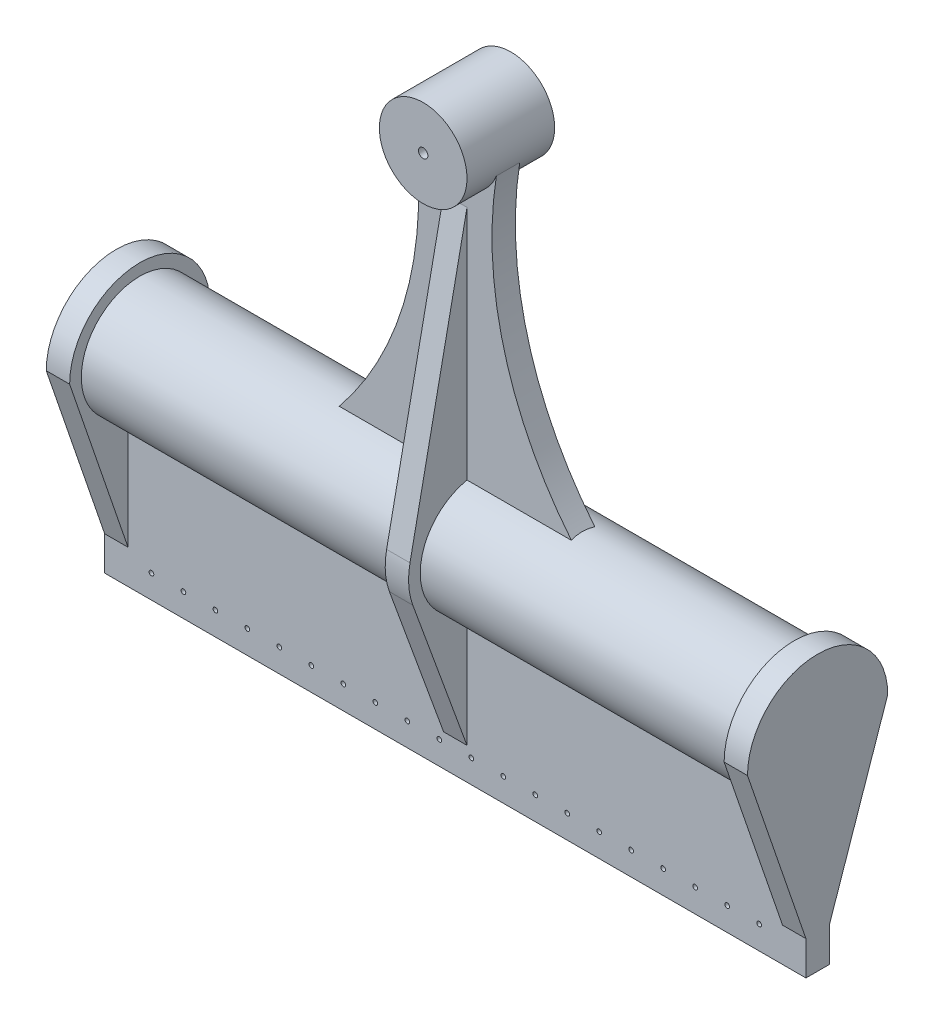
SolidWorks part; units mm, degrees
ref_plane "Front Plane" through (0, 0, 0) normal (1, 0, 0) x (0, 1, 0)
ref_plane "Top Plane" through (0, 0, 0) normal (0, 0, 1) x (0, 1, 0)
ref_plane "Right Plane" through (0, 0, 0) normal (0, 1, 0) x (-1, 0, 0)
sketch "Coefficients Plate Sketch" plane through (0, 0, 0) normal (0, 0, 1) x (0, 1, 0)
  line L1 (-44.45, -76.2) -> (0, -76.2)
  line L2 (-44.45, -76.2) -> (-44.45, 76.2)
  line L3 (-44.45, 76.2) -> (0, 76.2)
  line L4 (0, -76.2) -> (0, 76.2)
  line L5 (-44.45, -76.2) -> (0, 76.2) construction
  line L6 (-44.45, 76.2) -> (0, -76.2) construction
  circle A0 centre (-39.37, -66.04) radius 0.508
  circle A1 centre (-39.37, -59.0884) radius 0.508
  circle A2 centre (-39.37, -52.1368) radius 0.508
  circle A3 centre (-39.37, -45.1853) radius 0.508
  circle A4 centre (-39.37, -38.2337) radius 0.508
  circle A5 centre (-39.37, -31.2821) radius 0.508
  circle A6 centre (-39.37, -24.3305) radius 0.508
  circle A7 centre (-39.37, -17.3789) radius 0.508
  circle A8 centre (-39.37, -10.4274) radius 0.508
  circle A9 centre (-39.37, -3.4758) radius 0.508
  circle A10 centre (-39.37, 3.4758) radius 0.508
  circle A11 centre (-39.37, 10.4274) radius 0.508
  circle A12 centre (-39.37, 17.3789) radius 0.508
  circle A13 centre (-39.37, 24.3305) radius 0.508
  circle A14 centre (-39.37, 31.2821) radius 0.508
  circle A15 centre (-39.37, 38.2337) radius 0.508
  circle A16 centre (-39.37, 45.1853) radius 0.508
  circle A17 centre (-39.37, 52.1368) radius 0.508
  circle A18 centre (-39.37, 59.0884) radius 0.508
  circle A19 centre (-39.37, 66.04) radius 0.508
  point P0 (-22.225, 0)
extrude "Coefficients Plate" add sketch "Coefficients Plate Sketch" along normal blind 2.54 and the other way blind 2.54
sketch "Pivot Cylinder Sketch" plane through (0, 0, 0) normal (1, 0, 0) x (0, 1, 0)
  circle A0 centre (0, 0) radius 12.7
extrude "Pivot Cylinder" add sketch "Pivot Cylinder Sketch" along normal blind 76.2 and the other way blind 76.2
sketch "Edge Rib Front Sketch" plane through (0, 0, 0) normal (1, 0, 0) x (0, 1, 0)
  line L0 (0, 15.24) -> (-44.45, 0)
  line L1 (-44.45, 0) -> (0, -15.24)
  arc A0 (0, -15.24) -> (0, 15.24) centre (0, 0) ccw
extrude "Edge Rib Front" add sketch "Edge Rib Front Sketch" along normal blind 5.08 from offset 71.12
sketch "Edge Rib Back Sketch" plane through (0, 0, 0) normal (1, 0, 0) x (0, 1, 0)
  line L0 (0, 15.24) -> (-44.45, 0)
  line L1 (-44.45, 0) -> (0, -15.24)
  arc A0 (0, -15.24) -> (0, 15.24) centre (0, 0) ccw
extrude "Edge Rib Back" add sketch "Edge Rib Back Sketch" against normal blind 5.08 from offset 71.12 offset against normal yes
sketch "Summation Plate Sketch" plane through (0, 0, 0) normal (0, 0, 1) x (0, 1, 0)
  line L0 (0, -38.1) -> (0, 38.1)
  line L1 (76.2, 9.525) -> (76.2, -9.525)
  arc A0 (0, 38.1) -> (76.2, 9.525) centre (60.8501, 84.4794) ccw
  arc A1 (76.2, -9.525) -> (0, -38.1) centre (60.8501, -84.4794) ccw
extrude "Summation Plate" add sketch "Summation Plate Sketch" along normal blind 2.54 and the other way blind 2.54
sketch "Summation Anchor Sketch" plane through (0, 0, 0) normal (0, 0, 1) x (0, 1, 0)
  circle A0 centre (76.2, 0) radius 9.525
  circle A1 centre (76.2, 0) radius 1.016
extrude "Summation Anchor" add sketch "Summation Anchor Sketch" along normal blind 9.525 and the other way blind 9.525
sketch "Middle Rib Sketch" plane through (0, 0, 0) normal (1, 0, 0) x (0, 1, 0)
  line L0 (-44.45, 0) -> (-5.225, 14.3163)
  line L1 (-44.45, -2.54) -> (-44.45, 2.54) construction
  line L2 (3.0481, 14.9321) -> (76.2, 0)
  line L3 (76.2, 0) -> (3.0481, -14.9321)
  line L4 (-5.225, -14.3163) -> (-44.45, 0)
  line L5 (-44.45, 0) -> (76.2, 0) construction
  arc A0 (-5.225, 14.3163) -> (3.0481, 14.9321) centre (0.0001, 0) cw
  arc A1 (0, -15.24) -> (0, 15.24) centre (0, 0) ccw construction
  arc A2 (3.0481, -14.9321) -> (-5.225, -14.3163) centre (0.0001, 0) cw
extrude "Middle Rib" add sketch "Middle Rib Sketch" along normal blind 2.54 and the other way blind 2.54
